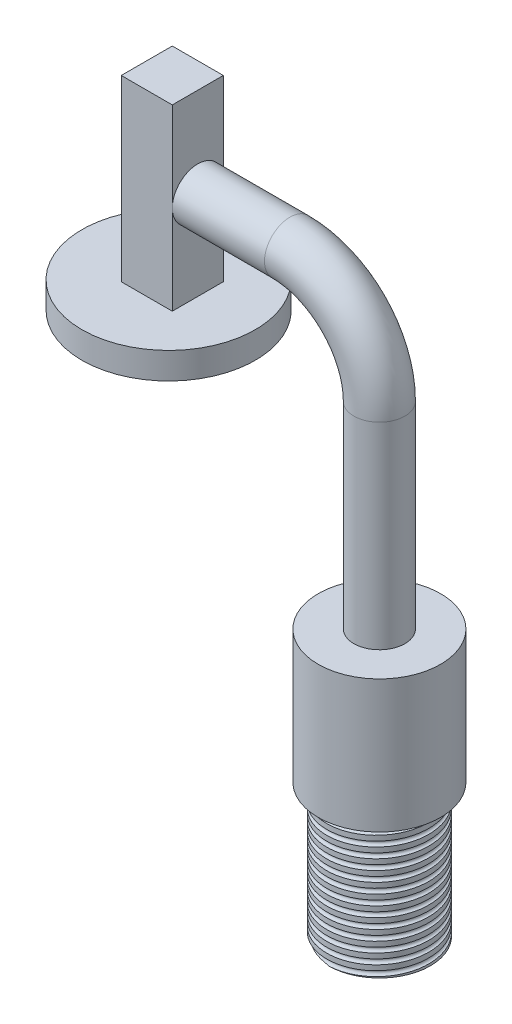
SolidWorks part; units mm, degrees
ref_plane "Front Plane" through (0, 0, 0) normal (0, 0, 1) x (1, 0, 0)
ref_plane "Top Plane" through (0, 0, 0) normal (0, 1, 0) x (1, 0, 0)
ref_plane "Right Plane" through (0, 0, 0) normal (1, 0, 0) x (0, 0, -1)
sketch "Sketch1" plane through (0, 0, 0) normal (0, 1, 0) x (1, 0, 0)
  circle A1 centre (0, 0) radius 50
extrude "Boss-Extrude1" add sketch "Sketch1" along normal blind 131
chamfer "Chamfer1" [suppressed] distance 5 angle 45
sketch "Sketch25" plane through (0, 0, 0) normal (0, -1, 0) x (1, 0, 0)
  circle A0 centre (0, 0) radius 50
curve "Helix/Spiral1" pitch 10 height 125 turns 12.5
sweep "Cut-Sweep3" cut path "Helix/Spiral1" align with end faces yes circular profile diameter 5 parameters "D3"=5
sketch "Sketch47" plane through (0, 131, 0) normal (0, 1, 0) x (1, 0, 0)
  circle A0 centre (0, 0) radius 60
extrude "Boss-Extrude2" add sketch "Sketch47" along normal blind 130
sketch "Sketch49" plane through (0, 0, 0) normal (0, 0, 1) x (1, 0, 0)
  line L0 (0, 261) -> (0, 454.1685)
  line L1 (60, 261) -> (-60, 261) construction
  line L2 (-87.6338, 541.8022) -> (-178.0194, 541.8022)
  arc A1 (0, 454.1685) -> (-87.6338, 541.8022) centre (-87.6338, 454.1685) ccw
sweep "Sweep1" add path "Sketch49" circular profile diameter 50 parameters "D3"=50
sketch "Sketch76" plane through (-178.0194, 0, 0) normal (-1, 0, 0) x (0, 0, 1)
  line L0 (-25, 454.1685) -> (-25, 261) construction
  line L1 (-25, 454.2368) -> (25, 454.2368)
  line L2 (-25, 454.2368) -> (-25, 629.3677)
  line L3 (-25, 629.3677) -> (25, 629.3677)
  line L4 (25, 454.2368) -> (25, 629.3677)
  line L5 (-25, 454.2368) -> (25, 629.3677) construction
  line L6 (-25, 629.3677) -> (25, 454.2368) construction
  point P0 (0, 541.8022)
extrude "Boss-Extrude3" add sketch "Sketch76" along normal blind 50
sketch "Sketch79" plane through (0, 454.2368, 0) normal (0, -1, 0) x (1, 0, 0)
  circle A0 centre (-206.6063, 0) radius 85
extrude "Boss-Extrude4" add sketch "Sketch79" along normal blind 26
sketch "Sketch80" plane through (0, 428.2368, 0) normal (0, -1, 0) x (1, 0, 0)
  line L1 (-221.3332, -17.6) -> (-191.1332, -17.6)
  line L2 (-223.8332, -15.1) -> (-223.8332, 15.1)
  line L3 (-221.3332, 17.6) -> (-191.1332, 17.6)
  line L4 (-188.6332, -15.1) -> (-188.6332, 15.1)
  arc A1 (-191.1332, 17.6) -> (-188.6332, 15.1) centre (-191.1332, 15.1) cw
  arc A2 (-191.1332, -17.6) -> (-188.6332, -15.1) centre (-191.1332, -15.1) ccw
  arc A3 (-221.3332, -17.6) -> (-223.8332, -15.1) centre (-221.3332, -15.1) cw
  arc A4 (-223.8332, 15.1) -> (-221.3332, 17.6) centre (-221.3332, 15.1) cw
  dimension "D1" = 2.5
extrude "Cut-Extrude1" cut sketch "Sketch80" against normal blind 18
